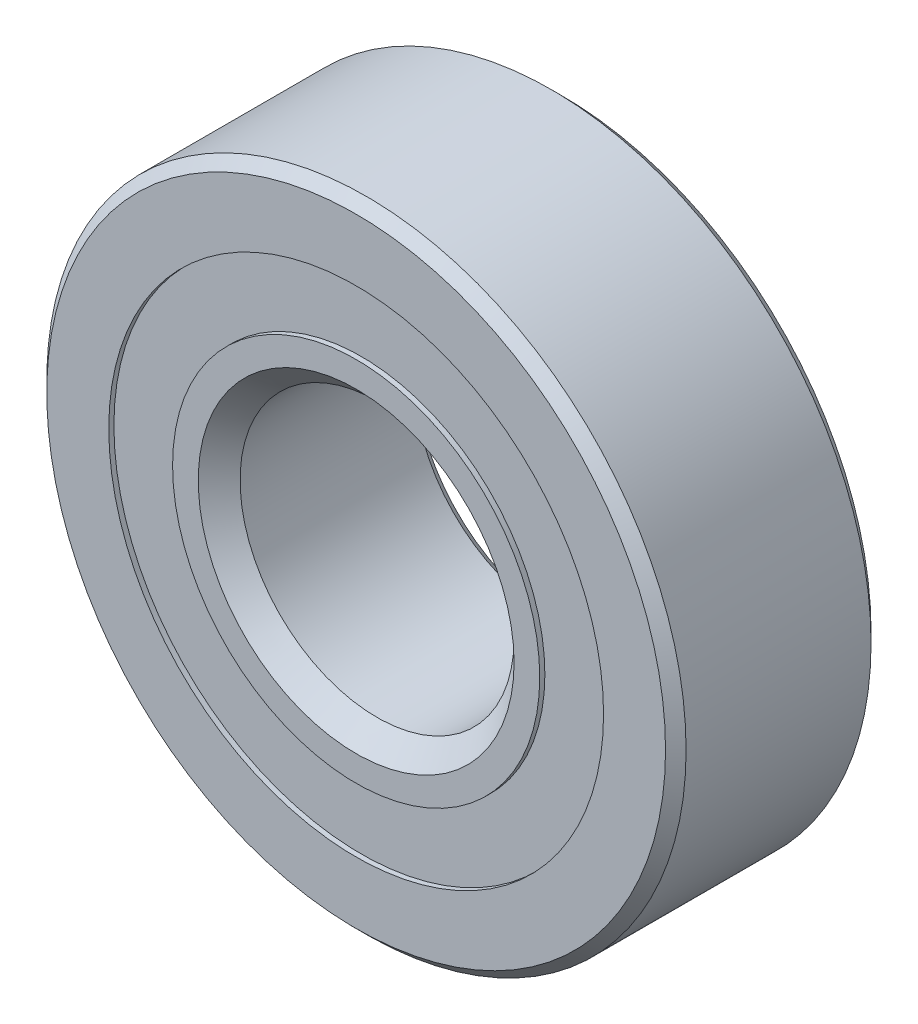
SolidWorks part; units mm, degrees
ref_plane "Front Plane" through (0, 0, 0) normal (0, 0, 1) x (1, 0, 0)
ref_plane "Top Plane" through (0, 0, 0) normal (0, 1, 0) x (1, 0, 0)
ref_plane "Right Plane" through (0, 0, 0) normal (1, 0, 0) x (0, 0, -1)
sketch "Sketch1" plane through (0, 0, 0) normal (1, 0, 0) x (0, 0, -1)
  line L0 (-3.5719, 0) -> (3.5719, 0) construction
  line L1 (0, 11.1125) -> (0, -11.1125) construction
  line L2 (3.2147, 11.1125) -> (-3.2147, 11.1125)
  line L3 (-3.2147, 11.1125) -> (-3.5719, 10.7553)
  line L4 (-3.5719, 10.7553) -> (-3.5719, 8.6004)
  line L5 (-3.5719, 8.6004) -> (-1.5875, 8.6004)
  line L6 (3.5719, 8.6004) -> (1.5875, 8.6004)
  line L7 (3.5719, 10.7553) -> (3.5719, 8.6004)
  line L8 (3.2147, 11.1125) -> (3.5719, 10.7553)
  line L9 (0, 11.1125) -> (0, 7.9375) construction
  line L10 (0, 7.9375) -> (0, 4.7625) construction
  arc A0 (-1.5875, 8.6004) -> (1.5875, 8.6004) centre (0, 7.9375) cw
  point P14 (0, 4.7625)
  dimension "Width" = 7.1437
  dimension "OD" = 22.225
  dimension "D1" = 45
  dimension "D2" = 0.3572
  dimension "D3" = 3.175
  dimension "D4" = 0.6629
revolve "Revolve1" add sketch "Sketch1" angle 360 about L0
sketch "Sketch2" plane through (0, 0, 0) normal (1, 0, 0) x (0, 0, -1)
  line L0 (-3.3933, 7.2746) -> (-1.5875, 7.2746)
  line L1 (-3.5719, 10.7553) -> (-3.5719, -10.7553) construction
  line L2 (-3.5719, 6.3822) -> (-3.3933, 6.3822) construction
  line L3 (-3.3933, 6.2036) -> (-2.6795, 5.4898)
  line L4 (-2.6795, 5.4898) -> (0, 5.4898)
  line L5 (0, 11.1125) -> (0, -11.1125) construction
  line L6 (0, 5.4898) -> (0, 6.2171)
  line L7 (0, 6.2171) -> (0, 4.7625) construction
  line L8 (-3.5719, 7.2746) -> (-3.5719, 5.4898) construction
  line L9 (-3.5719, 5.4898) -> (-2.6795, 5.4898) construction
  line L10 (-3.3933, 7.2746) -> (-3.3933, 6.2036)
  line L11 (-3.3933, 7.2746) -> (-3.3933, 10.9339) construction
  line L12 (-3.2147, 11.1125) -> (-3.5719, 10.7553) construction
  arc A0 (-1.5875, 7.2746) -> (0, 6.2171) centre (0, 7.9375) ccw
  arc A1 (1.5875, 8.6004) -> (-1.5875, 8.6004) centre (0, 7.9375) ccw construction
  circle A2 centre (0, 7.9375) radius 1.7204 construction
  dimension "D1" = 45
revolve "Revolve2" [suppressed] add sketch "Sketch2" angle 360 about L0
sketch "Sketch3" plane through (0, 0, 0) normal (1, 0, 0) x (0, 0, -1)
  line L0 (-3.3933, 6.2036) -> (-2.6795, 5.4898)
  line L1 (-2.6795, 5.4898) -> (0, 5.4898)
  line L2 (0, 5.4898) -> (0, 6.2171)
  line L3 (-3.5719, 6.3822) -> (-3.5719, 5.4898)
  line L4 (-3.5719, 7.2746) -> (-3.5719, 5.4898) construction
  line L5 (-3.5719, 5.4898) -> (-2.8446, 4.7625)
  line L6 (-2.8446, 4.7625) -> (3.2147, 4.7625)
  line L7 (3.2147, 11.1125) -> (3.2147, -11.1125) construction
  line L8 (3.2147, 4.7625) -> (3.5719, 5.1197)
  line L9 (3.5719, -10.7553) -> (3.5719, 10.7553) construction
  line L10 (3.5719, 5.1197) -> (3.5719, 7.2746)
  line L11 (3.5719, 7.2746) -> (1.5875, 7.2746)
  line L12 (-3.5719, 6.3822) -> (-3.3933, 6.3822)
  line L13 (3.2147, 11.1125) -> (3.5719, 10.7553) construction
  line L14 (-3.3933, 6.3822) -> (-3.3933, 6.2036)
  circle A0 centre (0, 7.9375) radius 1.7204 construction
  arc A1 (1.5875, 7.2746) -> (0, 6.2171) centre (0, 7.9375) cw
revolve "Revolve3" add sketch "Sketch3" angle 360 about L0
sketch "Sketch4" plane through (0, 0, 0) normal (1, 0, 0) x (0, 0, -1)
  line L0 (-1.7204, 7.9375) -> (1.7204, 7.9375)
  circle A1 centre (0, 7.9375) radius 1.7204 construction
  arc A2 (-1.7204, 7.9375) -> (1.7204, 7.9375) centre (0, 7.9375) cw
  arc A3 (1.5875, 8.6004) -> (-1.5875, 8.6004) centre (0, 7.9375) ccw construction
revolve "Revolve4" add sketch "Sketch4" angle 360 about L0
ref_axis "Axis1" through (0, 0, -3.5719) along (0, 0, 1)
pattern_circular "CirPattern1" count 12 every 30 about axis through (0, 0, -3.5719) along (0, 0, 1) of bodies 104
sketch "Sketch5" plane through (0, 0, 0) normal (1, 0, 0) x (0, 0, -1)
  line L0 (-3.5719, 8.6004) -> (-1.5875, 8.6004) construction
  line L1 (-3.3933, 8.6004) -> (-1.7204, 8.6004)
  line L2 (-3.3933, 8.6004) -> (-3.3933, 6.3822)
  line L3 (-3.3933, 6.3822) -> (-1.7204, 6.3822)
  line L4 (-1.7204, 8.6004) -> (-1.7204, 6.3822)
  line L6 (-3.2147, 11.1125) -> (-3.5719, 10.7553) construction
  line L7 (0, 11.1125) -> (0, 4.7625) construction
  line L8 (3.3933, 6.3822) -> (1.7204, 6.3822)
  line L9 (1.7204, 8.6004) -> (1.7204, 6.3822)
  line L10 (3.3933, 8.6004) -> (1.7204, 8.6004)
  line L11 (3.3933, 8.6004) -> (3.3933, 6.3822)
  circle A0 centre (0, 7.9375) radius 1.7204 construction
  point P10 (-3.3933, 10.9339)
revolve "Revolve5" add sketch "Sketch5" angle 360 about L0
equation "\"D2@Sketch1\" = \"Width@Sketch1\"*.05"
equation "\"D3@Sketch1\" = \"Width@Sketch1\"/2.25"
equation "\"D4@Sketch1\" = (((\"OD@Sketch1\"-\"Width@Sketch1\")/2)/3.25)/3.5"
equation "\"D2@CirPattern1\" = 360/\"Balls@CirPattern1\""
